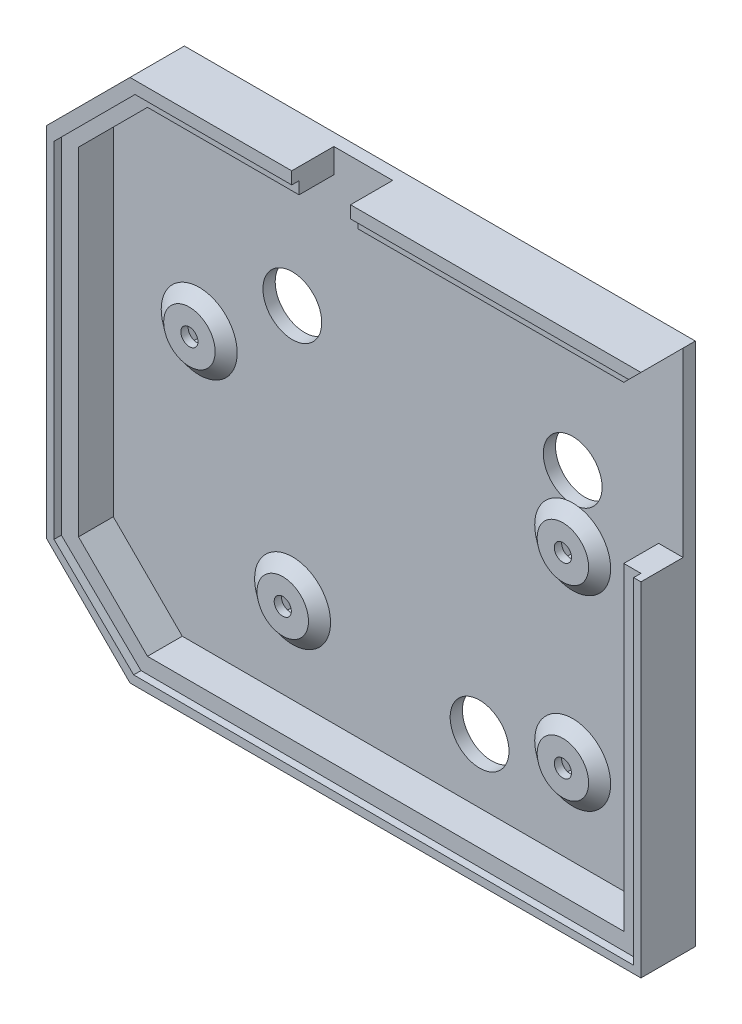
SolidWorks part; units mm, degrees
material "Delrin 2700 NC010, copolymère d'acétal à faible viscosité (SS)"
ref_plane "Plan de face" through (0, 0, 0) normal (0, 0, 1) x (1, 0, 0)
ref_plane "Plan de dessus" through (0, 0, 0) normal (0, 1, 0) x (1, 0, 0)
ref_plane "Plan de droite" through (0, 0, 0) normal (1, 0, 0) x (0, 0, -1)
sketch "Esquisse1" plane through (0, 0, 0) normal (0, 0, 1) x (1, 0, 0)
  line L0 (0, -85) -> (17, -102)
  line L4 (121.25, 5) -> (121.25, -102)
  line L5 (17, 5) -> (0, -12)
  line L7 (121.25, 5) -> (17, 5)
  line L8 (0, -12) -> (0, -85)
  line L9 (17, -102) -> (121.25, -102)
  dimension "D1" = 107
  dimension "D2" = 121.25
  dimension "D3" = 17
  dimension "D4" = 17
  dimension "D5" = 17
  dimension "D6" = 17
extrude "Boss.-Extru.1" add sketch "Esquisse1" along normal blind 2.5
sketch "Esquisse2" plane through (0, 0, 2.5) normal (0, 0, 1) x (1, 0, 0)
  line L0 (0, -12) -> (0, -85) construction
  line L1 (5, 0) -> (116.25, 0) construction
  line L2 (5, 0) -> (5, -97) construction
  line L3 (5, -97) -> (116.25, -97) construction
  line L4 (116.25, 0) -> (116.25, -97) construction
  line L5 (17, -102) -> (121.25, -102) construction
  line L6 (121.25, -102) -> (121.25, 5) construction
  line L7 (121.25, 5) -> (17, 5) construction
  line L8 (116.25, -32) -> (121.25, -32)
  line L9 (5, -82.9289) -> (19.0711, -97)
  line L10 (0, -85) -> (17, -102) construction
  line L11 (5, -14.0711) -> (19.0711, 0)
  line L12 (17, 5) -> (0, -12) construction
  line L14 (5, -14.0711) -> (5, -82.9289)
  line L15 (19.0711, -97) -> (116.25, -97)
  line L16 (121.25, 5) -> (121.25, -102) construction
  line L17 (121.25, -102) -> (17, -102)
  line L18 (17, -102) -> (0, -85)
  line L19 (0, -85) -> (0, -12)
  line L20 (0, -12) -> (17, 5)
  line L22 (116.25, 0) -> (121.25, 5)
  line L23 (116.25, -97) -> (116.25, -32)
  line L24 (121.25, -32) -> (121.25, -102)
  line L25 (50, 0) -> (50, 5)
  line L26 (62, 0) -> (62, 5)
  line L27 (19.0711, 0) -> (50, 0)
  line L28 (50, 5) -> (17, 5)
  line L29 (62, 5) -> (121.25, 5)
  line L30 (116.25, 0) -> (62, 0)
  point P33 (50, 0)
  point P34 (62, 0)
  dimension "D1" = 5
  dimension "D2" = 5
  dimension "D3" = 5
  dimension "D4" = 5
  dimension "D5" = 5
  dimension "D6" = 5
  dimension "D7" = 70
  dimension "D8" = 45
  dimension "D9" = 12
extrude "Boss.-Extru.2" add sketch "Esquisse2" along normal blind 8.6
sketch "Esquisse5" plane through (0, 0, 2.5) normal (0, 0, 1) x (1, 0, 0)
  line L0 (116.25, -97) -> (19.0711, -97) construction
  line L1 (116.25, -32) -> (116.25, -97) construction
  point P0 (22.525, -41.37)
  point P1 (98.725, -41.37)
  point P2 (98.725, -79.47)
  point P3 (41.575, -79.47)
  dimension "D1" = 38.1
  dimension "D2" = 17.53
  dimension "D3" = 17.525
  dimension "D4" = 76.2
  dimension "D5" = 57.15
ref_axis "Axe5" through (22.525, -41.37, 2.5) along (0, 0, 1)
ref_axis "Axe6" through (98.725, -41.37, 2.5) along (0, 0, 1)
ref_axis "Axe7" through (41.575, -79.47, 2.5) along (0, 0, 1)
ref_axis "Axe8" through (98.725, -79.47, 2.5) along (0, 0, 1)
sketch3d "Esquisse3D5"
  line L0 (22.525, -41.37, 2.5) -> (98.725, -41.37, 2.5) construction
  line L1 (41.575, -79.47, 2.5) -> (98.725, -79.47, 2.5) construction
ref_plane "Plan4" through (98.725, -41.37, 2.5) normal (1, 0, 0) x (0, 0, -1)
sketch "Esquisse8" plane through (98.725, -41.37, 2.5) normal (1, 0, 0) x (0, 0, -1)
  line L0 (0, 1.75) -> (0, 7.75)
  line L1 (0, 7.75) -> (-2, 5.25)
  line L2 (-2, 5.25) -> (-2, 1.75)
  line L3 (-2, 1.75) -> (0, 1.75)
  line L5 (0, 0) -> (-50.5083, 0) construction
  point P0 (0, 1.75)
  dimension "D1" = 6
  dimension "D2" = 3.5
  dimension "D3" = 2
  dimension "D4" = 1.75
revolve "Révolution3" add sketch "Esquisse8" angle 360 about axis through (98.725, -41.37, 2.5) along (0, 0, 1)
ref_plane "Plan5" through (41.575, -79.47, 2.5) normal (1, 0, 0) x (0, 0, -1)
sketch "Esquisse9" plane through (41.575, -79.47, 2.5) normal (1, 0, 0) x (0, 0, -1)
  line L0 (0, 1.75) -> (0, 7.75)
  line L1 (0, 7.75) -> (-2, 5.25)
  line L2 (-2, 5.25) -> (-2, 1.75)
  line L3 (-2, 1.75) -> (0, 1.75)
  point P0 (0, 1.75)
  dimension "D1" = 2
  dimension "D2" = 6
  dimension "D3" = 3.5
  dimension "D4" = 1.75
revolve "Révolution4" add sketch "Esquisse9" angle 360 about axis through (41.575, -79.47, 2.5) along (0, 0, 1)
ref_plane "Plan6" through (98.725, -79.47, 2.5) normal (1, 0, 0) x (0, 0, -1)
sketch "Esquisse10" plane through (98.725, -79.47, 2.5) normal (1, 0, 0) x (0, 0, -1)
  line L0 (0, 1.75) -> (0, 7.75)
  line L1 (0, 7.75) -> (-2, 5.25)
  line L2 (-2, 5.25) -> (-2, 1.75)
  line L3 (-2, 1.75) -> (0, 1.75)
  point P0 (0, 1.75)
  dimension "D1" = 6
  dimension "D2" = 2
  dimension "D3" = 3.5
  dimension "D4" = 1.75
revolve "Révolution5" add sketch "Esquisse10" angle 360 about axis through (98.725, -79.47, 2.5) along (0, 0, 1)
hole_wizard "Dégagement M32" positions "Esquisse15" profile "Esquisse16" hole size "M3" standard "Ansi Metric" end condition up to next
sketch "Esquisse15" plane through (0, 0, 2.5) normal (0, 0, 1) x (1, 0, 0)
  point P0 (22.525, -41.37)
  point P3 (41.575, -79.47)
  point P6 (98.725, -41.37)
  point P9 (98.725, -79.47)
sketch "Esquisse16" plane through (22.525, -41.37, 2.5) normal (1, 0, 0) x (0, -1, 0)
  line L0 (0, 0) -> (0, 2.5)
  line L1 (0, 2.5) -> (1.8, 2.5)
  line L2 (1.8, 2.5) -> (1.8, 0)
  line L5 (1.8, 0) -> (0, 0)
  line L11 (0, -6.35) -> (0, 107.95) construction
  dimension "Diamètre du perçage jusqu'au prochain" = 3.6
  dimension "Profondeur du perçage jusqu'au prochain" = 2.5
ref_plane "Plan7" through (22.525, -41.37, 2.5) normal (1, 0, 0) x (0, 0, -1)
sketch "Esquisse17" plane through (22.525, -41.37, 2.5) normal (1, 0, 0) x (0, 0, -1)
  line L1 (0, 1.75) -> (0, 7.75)
  line L2 (0, 7.75) -> (-2, 5.25)
  line L3 (-2, 5.25) -> (-2, 1.75)
  line L4 (-2, 1.75) -> (0, 1.75)
  line L5 (0, 0) -> (-51.036, 0) construction
  dimension "D1" = 1.75
  dimension "D2" = 6
  dimension "D3" = 3.5
  dimension "D4" = 2
revolve "Révolution6" add sketch "Esquisse17" angle 360 about axis through (22.525, -41.37, 2.5) along (0, 0, 1)
ref_point "Point1"
ref_point "Point2"
ref_point "Point3"
ref_point "Point4"
sketch "Esquisse18" plane through (0, 0, 0) normal (0, 0, -1) x (-1, 0, 0)
  line L1 (-97.1662, -76.77) -> (-100.2838, -76.77)
  line L2 (-100.2838, -76.77) -> (-101.8427, -79.47)
  line L3 (-101.8427, -79.47) -> (-100.2838, -82.17)
  line L4 (-100.2838, -82.17) -> (-97.1662, -82.17)
  line L5 (-97.1662, -82.17) -> (-95.6073, -79.47)
  line L6 (-95.6073, -79.47) -> (-97.1662, -76.77)
  line L7 (-97.1662, -38.67) -> (-100.2838, -38.67)
  line L8 (-100.2838, -38.67) -> (-101.8427, -41.37)
  line L9 (-101.8427, -41.37) -> (-100.2838, -44.07)
  line L10 (-100.2838, -44.07) -> (-97.1662, -44.07)
  line L11 (-97.1662, -44.07) -> (-95.6073, -41.37)
  line L12 (-95.6073, -41.37) -> (-97.1662, -38.67)
  line L13 (-19.4073, -41.37) -> (-20.9662, -38.67)
  line L14 (-20.9662, -38.67) -> (-24.0838, -38.67)
  line L15 (-24.0838, -38.67) -> (-25.6427, -41.37)
  line L16 (-25.6427, -41.37) -> (-24.0838, -44.07)
  line L17 (-24.0838, -44.07) -> (-20.9662, -44.07)
  line L18 (-20.9662, -44.07) -> (-19.4073, -41.37)
  line L19 (-38.4573, -79.47) -> (-40.0162, -76.77)
  line L20 (-40.0162, -76.77) -> (-43.1338, -76.77)
  line L21 (-43.1338, -76.77) -> (-44.6927, -79.47)
  line L22 (-44.6927, -79.47) -> (-43.1338, -82.17)
  line L23 (-43.1338, -82.17) -> (-40.0162, -82.17)
  line L24 (-40.0162, -82.17) -> (-38.4573, -79.47)
  line L26 (-17, -102) -> (-121.25, -102) construction
  circle A0 centre (-98.725, -79.47) radius 2.7 construction
  circle A1 centre (-98.725, -41.37) radius 2.7 construction
  circle A2 centre (-22.525, -41.37) radius 2.7 construction
  circle A3 centre (-41.575, -79.47) radius 2.7 construction
  dimension "D1" = 5.4
  dimension "D2" = 5.4
  dimension "D3" = 5.4
  dimension "D4" = 5.4
extrude "Enlèv. mat.-Extru.2" cut sketch "Esquisse18" against normal blind 3
sketch "Esquisse20" plane through (0, 0, 11.1) normal (0, 0, 1) x (1, 0, 0)
  line L1 (119.75, 2.5) -> (18.0355, 2.5)
  line L2 (5, -82.9289) -> (0, -85) construction
  line L3 (17, -102) -> (19.0711, -97) construction
  line L4 (116.25, -97) -> (121.25, -102) construction
  line L5 (121.25, 5) -> (116.25, 0) construction
  line L12 (121.25, 5) -> (62, 5) construction
  line L13 (1.5, 2.5) -> (119.75, 2.5) construction
  line L14 (1.5, 2.5) -> (1.5, -100.5) construction
  line L15 (1.5, -100.5) -> (119.75, -100.5) construction
  line L16 (119.75, 2.5) -> (119.75, -100.5) construction
  line L17 (121.25, -32) -> (121.25, 5) construction
  line L18 (17, -102) -> (121.25, -102) construction
  line L19 (0, -12) -> (0, -85) construction
  line L23 (1.5, -84.3787) -> (17.7514, -100.186)
  line L24 (17.7514, -100.186) -> (119.75, -100.5)
  line L25 (119.75, -100.5) -> (119.75, 2.5)
  line L26 (39.1913, 23.6558) -> (-16.7593, -32.2949) construction
  line L27 (17, 5) -> (0, -12) construction
  line L28 (18.0355, 2.5) -> (1.5, -14.0355)
  line L29 (1.5, -14.0355) -> (1.5, -84.3787)
  dimension "D1" = 2.5
  dimension "D2" = 1.5
  dimension "D3" = 1.5
  dimension "D4" = 1.5
  dimension "D5" = 2.5
extrude "Enlèv. mat.-Extru.3" cut sketch "Esquisse20" against normal blind 1.5
sketch "Esquisse21" plane through (0, 0, 2.5) normal (0, 0, 1) x (1, 0, 0)
  circle A0 centre (98.725, -27.87) radius 6
  circle A1 centre (41.525, -27.37) radius 6
  circle A2 centre (79.725, -83.97) radius 6
  dimension "D1" = 13.5
  dimension "D2" = 14
  dimension "D4" = 19
  dimension "D3" = 19
  dimension "D5" = 4.5
extrude "Enlèv. mat.-Extru.4" cut sketch "Esquisse21" against normal blind 10
